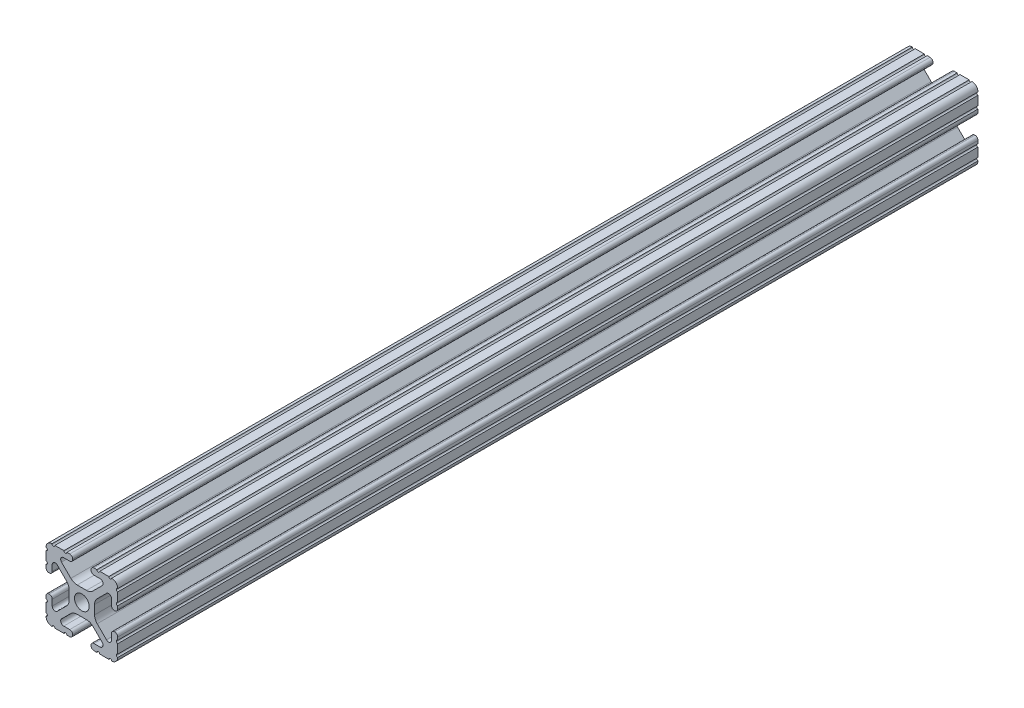
SolidWorks part; units mm, degrees
material "McMaster 6105-T5"
ref_plane "Front Plane" through (0, 0, 0) normal (0, 0, 1) x (1, 0, 0)
ref_plane "Top Plane" through (0, 0, 0) normal (0, 1, 0) x (1, 0, 0)
ref_plane "Right Plane" through (0, 0, 0) normal (1, 0, 0) x (0, 0, -1)
sketch "Sketch1" plane through (0, 0, 0) normal (0, 0, 1) x (1, 0, 0)
  line L88 (-7.1797, -8.6452) -> (-3.9523, -5.4237)
  line L89 (-1.7093, -4.4958) -> (1.7093, -4.4958)
  line L90 (3.9523, -5.4237) -> (7.1797, -8.6452)
  line L91 (6.4164, -10.4902) -> (4.2875, -10.4902)
  line L92 (3.2385, -11.5392) -> (3.2385, -11.651)
  line L93 (4.2875, -12.7) -> (5.3171, -12.7)
  line L94 (6.3331, -12.7) -> (9.5504, -12.7)
  line L95 (12.7, -9.5504) -> (12.7, -6.3331)
  line L96 (12.7, -5.3171) -> (12.7, -4.2875)
  line L97 (11.651, -3.2385) -> (11.5392, -3.2385)
  line L98 (10.4902, -4.2875) -> (10.4902, -6.4021)
  line L99 (8.7371, -7.1294) -> (5.441, -3.8408)
  line L100 (4.5085, -1.5932) -> (4.5085, 1.5932)
  line L101 (5.441, 3.8408) -> (8.7371, 7.1294)
  line L102 (10.4902, 6.4021) -> (10.4902, 4.2875)
  line L103 (11.5392, 3.2385) -> (11.651, 3.2385)
  line L104 (12.7, 4.2875) -> (12.7, 5.3171)
  line L105 (12.7, 6.3331) -> (12.7, 9.5504)
  line L106 (9.5504, 12.7) -> (6.3331, 12.7)
  line L107 (5.3171, 12.7) -> (4.2875, 12.7)
  line L108 (3.2385, 11.651) -> (3.2385, 11.5392)
  line L109 (4.2875, 10.4902) -> (6.4768, 10.4902)
  line L110 (7.207, 8.7244) -> (3.8983, 5.4232)
  line L111 (1.6558, 4.4958) -> (-1.6558, 4.4958)
  line L112 (-3.8983, 5.4232) -> (-7.207, 8.7244)
  line L113 (-6.4768, 10.4902) -> (-4.2875, 10.4902)
  line L114 (-3.2385, 11.5392) -> (-3.2385, 11.651)
  line L115 (-4.2875, 12.7) -> (-5.3171, 12.7)
  line L116 (-6.3331, 12.7) -> (-9.5504, 12.7)
  line L117 (-12.7, 9.5504) -> (-12.7, 6.3331)
  line L118 (-12.7, 5.3171) -> (-12.7, 4.2875)
  line L119 (-11.651, 3.2385) -> (-11.5392, 3.2385)
  line L120 (-10.4902, 4.2875) -> (-10.4902, 6.4021)
  line L121 (-8.7371, 7.1294) -> (-5.441, 3.8408)
  line L122 (-4.5085, 1.5932) -> (-4.5085, -1.5932)
  line L123 (-5.441, -3.8408) -> (-8.7371, -7.1294)
  line L124 (-10.4902, -6.4021) -> (-10.4902, -4.2875)
  line L125 (-11.5392, -3.2385) -> (-11.651, -3.2385)
  line L126 (-12.7, -4.2875) -> (-12.7, -5.3171)
  line L127 (-12.7, -6.3331) -> (-12.7, -9.5504)
  line L128 (-9.5504, -12.7) -> (-6.3331, -12.7)
  line L129 (-5.3171, -12.7) -> (-4.2875, -12.7)
  line L130 (-3.2385, -11.651) -> (-3.2385, -11.5392)
  line L131 (-4.2875, -10.4902) -> (-6.4164, -10.4902)
  circle A1 centre (0, 0) radius 2.6035
  arc A104 (-7.1797, -8.6452) -> (-6.4164, -10.4902) centre (-6.4164, -9.4098) ccw
  arc A105 (-1.7093, -4.4958) -> (-3.9523, -5.4237) centre (-1.7093, -7.6708) ccw
  arc A106 (3.9523, -5.4237) -> (1.7093, -4.4958) centre (1.7093, -7.6708) ccw
  arc A107 (6.4164, -10.4902) -> (7.1797, -8.6452) centre (6.4164, -9.4098) ccw
  arc A108 (4.2875, -10.4902) -> (3.2385, -11.5392) centre (4.2875, -11.5392) ccw
  arc A109 (3.2385, -11.651) -> (4.2875, -12.7) centre (4.2875, -11.651) ccw
  arc A110 (6.3331, -12.7) -> (5.3171, -12.7) centre (5.8251, -12.7) ccw
  arc A111 (10.5664, -12.6998) -> (9.5504, -12.7) centre (10.0584, -12.7) ccw
  arc A112 (10.5664, -12.6998) -> (12.6998, -10.5664) centre (10.5918, -10.5918) ccw
  arc A113 (12.7, -9.5504) -> (12.6998, -10.5664) centre (12.7, -10.0584) ccw
  arc A114 (12.7, -5.3171) -> (12.7, -6.3331) centre (12.7, -5.8251) ccw
  arc A115 (12.7, -4.2875) -> (11.651, -3.2385) centre (11.651, -4.2875) ccw
  arc A116 (11.5392, -3.2385) -> (10.4902, -4.2875) centre (11.5392, -4.2875) ccw
  arc A117 (8.7371, -7.1294) -> (10.4902, -6.4021) centre (9.4628, -6.4021) ccw
  arc A118 (4.5085, -1.5932) -> (5.441, -3.8408) centre (7.6835, -1.5932) ccw
  arc A119 (5.441, 3.8408) -> (4.5085, 1.5932) centre (7.6835, 1.5932) ccw
  arc A120 (10.4902, 6.4021) -> (8.7371, 7.1294) centre (9.4628, 6.4021) ccw
  arc A121 (10.4902, 4.2875) -> (11.5392, 3.2385) centre (11.5392, 4.2875) ccw
  arc A122 (11.651, 3.2385) -> (12.7, 4.2875) centre (11.651, 4.2875) ccw
  arc A123 (12.7, 6.3331) -> (12.7, 5.3171) centre (12.7, 5.8251) ccw
  arc A124 (12.6998, 10.5664) -> (12.7, 9.5504) centre (12.7, 10.0584) ccw
  arc A125 (12.6998, 10.5664) -> (10.5664, 12.6998) centre (10.5918, 10.5918) ccw
  arc A126 (9.5504, 12.7) -> (10.5664, 12.6998) centre (10.0584, 12.7) ccw
  arc A127 (5.3171, 12.7) -> (6.3331, 12.7) centre (5.8251, 12.7) ccw
  arc A128 (4.2875, 12.7) -> (3.2385, 11.651) centre (4.2875, 11.651) ccw
  arc A129 (3.2385, 11.5392) -> (4.2875, 10.4902) centre (4.2875, 11.5392) ccw
  arc A130 (7.207, 8.7244) -> (6.4768, 10.4902) centre (6.4768, 9.4563) ccw
  arc A131 (1.6558, 4.4958) -> (3.8983, 5.4232) centre (1.6558, 7.6708) ccw
  arc A132 (-3.8983, 5.4232) -> (-1.6558, 4.4958) centre (-1.6558, 7.6708) ccw
  arc A133 (-6.4768, 10.4902) -> (-7.207, 8.7244) centre (-6.4768, 9.4563) ccw
  arc A134 (-4.2875, 10.4902) -> (-3.2385, 11.5392) centre (-4.2875, 11.5392) ccw
  arc A135 (-3.2385, 11.651) -> (-4.2875, 12.7) centre (-4.2875, 11.651) ccw
  arc A136 (-6.3331, 12.7) -> (-5.3171, 12.7) centre (-5.8251, 12.7) ccw
  arc A137 (-10.5664, 12.6998) -> (-9.5504, 12.7) centre (-10.0584, 12.7) ccw
  arc A138 (-10.5664, 12.6998) -> (-12.6998, 10.5664) centre (-10.5918, 10.5918) ccw
  arc A139 (-12.7, 9.5504) -> (-12.6998, 10.5664) centre (-12.7, 10.0584) ccw
  arc A140 (-12.7, 5.3171) -> (-12.7, 6.3331) centre (-12.7, 5.8251) ccw
  arc A141 (-12.7, 4.2875) -> (-11.651, 3.2385) centre (-11.651, 4.2875) ccw
  arc A142 (-11.5392, 3.2385) -> (-10.4902, 4.2875) centre (-11.5392, 4.2875) ccw
  arc A143 (-8.7371, 7.1294) -> (-10.4902, 6.4021) centre (-9.4628, 6.4021) ccw
  arc A144 (-4.5085, 1.5932) -> (-5.441, 3.8408) centre (-7.6835, 1.5932) ccw
  arc A145 (-5.441, -3.8408) -> (-4.5085, -1.5932) centre (-7.6835, -1.5932) ccw
  arc A146 (-10.4902, -6.4021) -> (-8.7371, -7.1294) centre (-9.4628, -6.4021) ccw
  arc A147 (-10.4902, -4.2875) -> (-11.5392, -3.2385) centre (-11.5392, -4.2875) ccw
  arc A148 (-11.651, -3.2385) -> (-12.7, -4.2875) centre (-11.651, -4.2875) ccw
  arc A149 (-12.7, -6.3331) -> (-12.7, -5.3171) centre (-12.7, -5.8251) ccw
  arc A150 (-12.6998, -10.5664) -> (-12.7, -9.5504) centre (-12.7, -10.0584) ccw
  arc A151 (-12.6998, -10.5664) -> (-10.5664, -12.6998) centre (-10.5918, -10.5918) ccw
  arc A152 (-9.5504, -12.7) -> (-10.5664, -12.6998) centre (-10.0584, -12.7) ccw
  arc A153 (-5.3171, -12.7) -> (-6.3331, -12.7) centre (-5.8251, -12.7) ccw
  arc A154 (-4.2875, -12.7) -> (-3.2385, -11.651) centre (-4.2875, -11.651) ccw
  arc A155 (-3.2385, -11.5392) -> (-4.2875, -10.4902) centre (-4.2875, -11.5392) ccw
extrude "Boss-Extrude1" add sketch "Sketch1" along normal mid plane 304.8
sketch "Sketch2" plane through (0, 12.7, 0) normal (0, 1, 0) x (1, 0, 0)
  line L0 (0, -155.4789) -> (0, 151.1822) construction
  line L1 (1.6558, -152.4) -> (-1.6558, -152.4) construction
  line L2 (1.6558, 152.4) -> (-1.6558, 152.4) construction
  circle A0 centre (0, -88.9) radius 3.175
  circle A1 centre (0, 127) radius 3.175
  point P4 (0, -152.4)
  point P12 (0, 152.4)
  dimension "D3" = 6.35
  dimension "D1" = 63.5
  dimension "D2" = 25.4
extrude "Cut-Extrude1" cut sketch "Sketch2" against normal through all both and the other way through all
